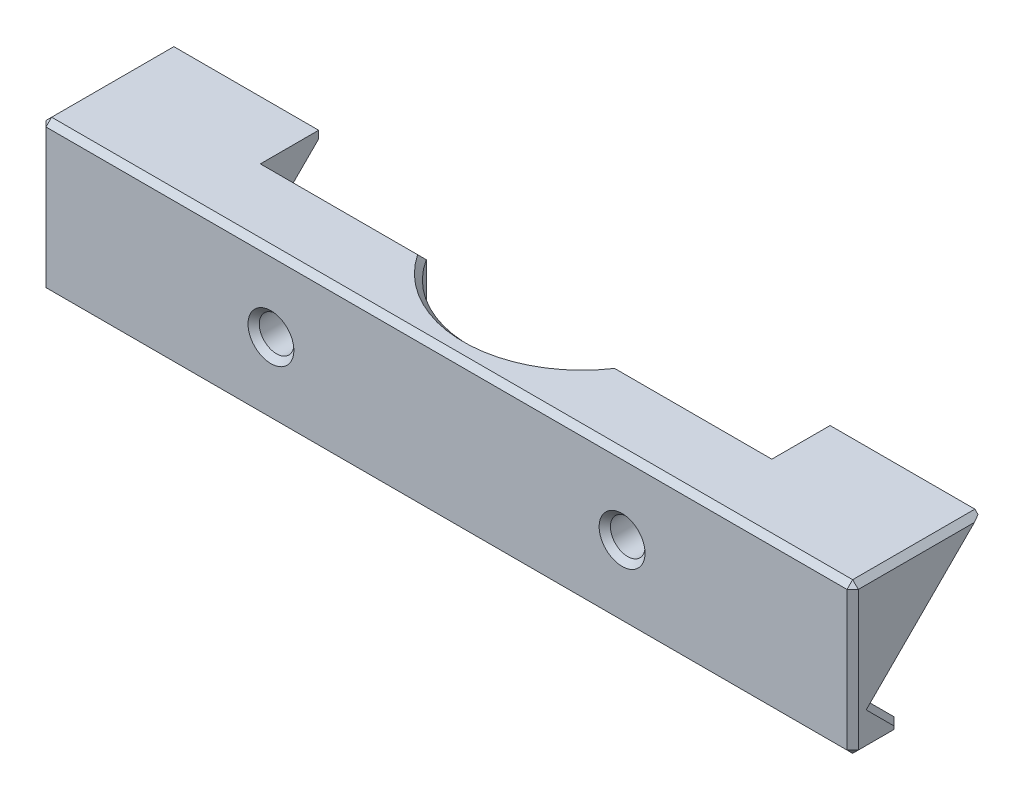
SolidWorks part; units mm, degrees
ref_plane "Front" through (0, 0, 0) normal (0, 0, 1) x (1, 0, 0)
ref_plane "Top" through (0, 0, 0) normal (0, 1, 0) x (1, 0, 0)
ref_plane "Right" through (0, 0, 0) normal (1, 0, 0) x (0, 0, -1)
sketch "Skizze1" plane through (0, 0, 0) normal (0, 0, 1) x (1, 0, 0)
  line L0 (0, 0) -> (0, 36.2286) construction
  line L1 (34, 0) -> (-34, 0)
  line L2 (-34, 0) -> (-34, 20)
  line L3 (-34, 20) -> (34, 20)
  line L4 (34, 0) -> (34, 20)
  point P7 (0, 20)
  dimension "D1" = 20
extrude "Aufsatz-Linear austragen1" add sketch "Skizze1" along normal blind 10
sketch "Skizze2" plane through (-34, 0, 0) normal (-1, 0, 0) x (0, 0, 1)
  line L1 (7.1421, 4.8579) -> (-7, 19)
  line L5 (0, 20) -> (10, 20)
  line L6 (10, 20) -> (0, 20) construction
  line L7 (10, 20) -> (10, 0)
  line L8 (10, 0) -> (2.2843, 0)
  line L9 (10, 0) -> (0, 0) construction
  line L10 (2.2843, 0) -> (7.1421, 4.8579)
  line L15 (-7, 19) -> (-7, 20)
  line L16 (142, 20) -> (-158, 20) construction
  line L17 (-7, 20) -> (0, 20)
  line L18 (7.1421, 4.8579) -> (-63.5685, -65.8528) construction
extrude "Aufsatz-Linear austragen2" add sketch "Skizze2" along normal blind 20
mirror "Spiegeln1" about plane through (0, 0, 0) normal (1, 0, 0) of "Aufsatz-Linear austragen2"
sketch "Skizze3" plane through (0, 0, 0) normal (0, -1, 0) x (1, 0, 0)
  line L0 (0, 0) -> (0, -17.264) construction
  circle A0 centre (0, -8) radius 15
  dimension "D1" = 30
extrude "Schnitt-Linear austragen1" cut sketch "Skizze3" against normal blind 20
sketch "Skizze4" plane through (0, 0, 0) normal (0, 0, -1) x (-1, 0, 0)
  line L0 (-12.6886, 10) -> (-34, 10) construction
  line L1 (-12.6886, 0) -> (-12.6886, 20) construction
  line L2 (-34, 12) -> (-34, 4.8579) construction
  line L3 (0, 0) -> (0, 20) construction
  line L4 (12.6886, 20) -> (-12.6886, 20) construction
  circle A0 centre (-23.3443, 10) radius 2.3
  circle A1 centre (23.3443, 10) radius 2.3
  dimension "D1" = 4.6
extrude "Schnitt-Linear austragen2" cut sketch "Skizze4" against normal blind 10
sketch "Skizze5" plane through (0, 0, 0) normal (0, 0, -1) x (-1, 0, 0)
  circle A0 centre (-23.3443, 10) radius 3.75
  circle A1 centre (23.3443, 10) radius 3.75
  dimension "D1" = 7.5
extrude "Schnitt-Linear austragen3" cut sketch "Skizze5" against normal blind 3
sketch "Skizze6" plane through (54, 0, 0) normal (1, 0, 0) x (0, 0, -1)
  line L0 (-3.7843, 1.5) -> (-3.7843, 0)
  line L1 (-7.1421, 4.8579) -> (-2.2843, 0) construction
  line L2 (-2.2843, 0) -> (-10, 0) construction
  line L3 (-3.7843, 0) -> (-1.8311, -0.9493)
  line L4 (-1.8311, -0.9493) -> (-1.3963, 1.5278)
  line L5 (-1.3963, 1.5278) -> (-3.7843, 1.5)
  dimension "D1" = 1.5
extrude "Schnitt-Linear austragen4" cut sketch "Skizze6" against normal blind 20
mirror "Spiegeln2" about plane through (0, 0, 0) normal (1, 0, 0) of "Schnitt-Linear austragen4"
chamfer "Fase1" distance 0.75 angle 45 26 edges at (-21.0443, 10, 10) (21.0443, 10, 10) (54, 20, 1.5) (54, 11.9289, 0.0711) (54, 3.1789, 5.4632) (54, 0.75, 3.7843) (-54, 0, 6.8921) (54, 10, 10) (0, 20, 10) (-54, 10, 10) (0, 0, 10) (54, 0, 6.8921) (44, 0, 3.7843) (34, 0, 1.8921) (23.3443, 0, 0) (0, 0, 7) (-23.3443, 0, 0) (-34, 0, 1.8921) (-44, 0, 3.7843) (-54, 0.75, 3.7843) (-54, 3.1789, 5.4632) (-54, 11.9289, 0.0711) (-23.3443, 20, 0) (0, 20, 7) (23.3443, 20, 0) (-54, 20, 1.5)
fillet "Verrundung1" radius 2 2 edges at (34, 15.625, 0) (-34, 15.625, 0)
